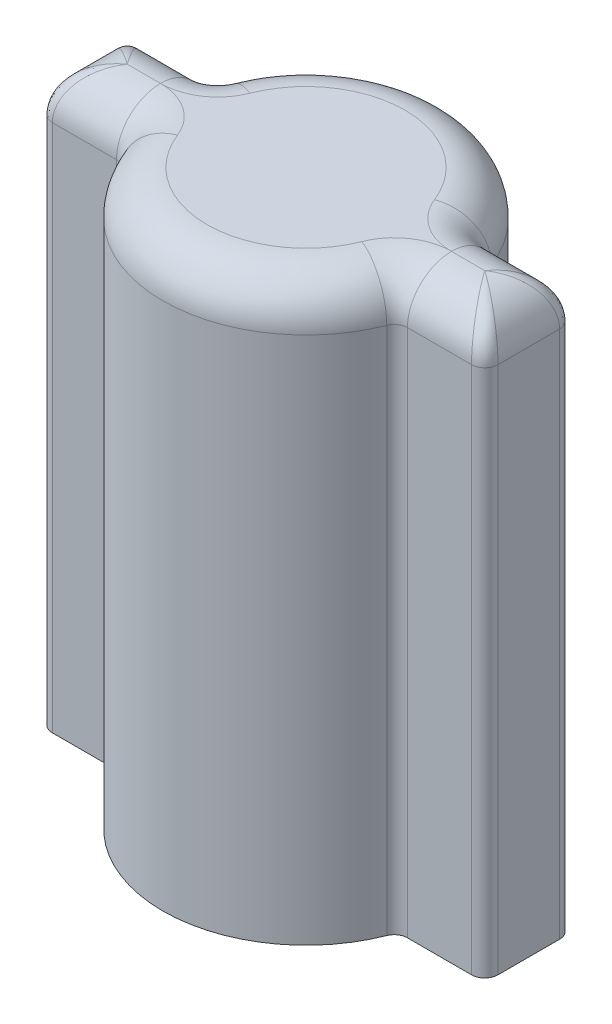
SolidWorks part; units mm, degrees
ref_plane "Front" through (0, 0, 0) normal (0, 0, 1) x (1, 0, 0)
ref_plane "Top" through (0, 0, 0) normal (0, 1, 0) x (1, 0, 0)
ref_plane "Right" through (0, 0, 0) normal (1, 0, 0) x (0, 0, -1)
sketch "Sketch1" plane through (0, 0, 0) normal (0, 1, 0) x (1, 0, 0)
  circle A0 centre (0, 0) radius 3.25
  dimension "D1" = 6.5
extrude "Boss-Extrude1" add sketch "Sketch1" along normal blind 13
sketch "Sketch2" plane through (0, 0, 0) normal (0, 1, 0) x (1, 0, 0)
  line L0 (-5.0593, 0) -> (5.0593, 0)
  point P2 (0, 0)
  point P4 (3.2396, 0)
  point P5 (4.0648, 0)
  point P6 (5.0593, 0)
extrude "Extrude-Thin1" add sketch "Sketch2" along normal blind 13 thin thin type mid plane wall 2
fillet "Fillet1" radius 0.3 8 edges at (3.0923, 6.5, -1) (5.0593, 6.5, -1) (3.0923, 6.5, 1) (-3.0923, 6.5, 1) (-5.0593, 6.5, 1) (-5.0593, 6.5, -1) (-3.0923, 6.5, -1) (5.0593, 6.5, 1)
fillet "Fillet2" radius 1 16 edges at (4.9715, 13, 0.9121) (4.0314, 13, 1) (3.1345, 13, 1.0521) (0, 13, 3.25) (-3.1345, 13, 1.0521) (-4.0314, 13, 1) (-4.9715, 13, 0.9121) (-5.0593, 13, 0) (-4.9715, 13, -0.9121) (-4.0314, 13, -1) (-3.1345, 13, -1.0521) (0, 13, -3.25) (3.1345, 13, -1.0521) (4.0314, 13, -1) (4.9715, 13, -0.9121) (5.0593, 13, 0)
sketch "Sketch3" plane through (0, 0, 0) normal (0, -1, 0) x (1, 0, 0)
  circle A0 centre (0, 0) radius 1
  dimension "D1" = 2
extrude "Cut-Extrude1" cut sketch "Sketch3" against normal blind 11
chamfer "Chamfer1" distance 1 angle 45 1 edges at (0, 0, -1)
